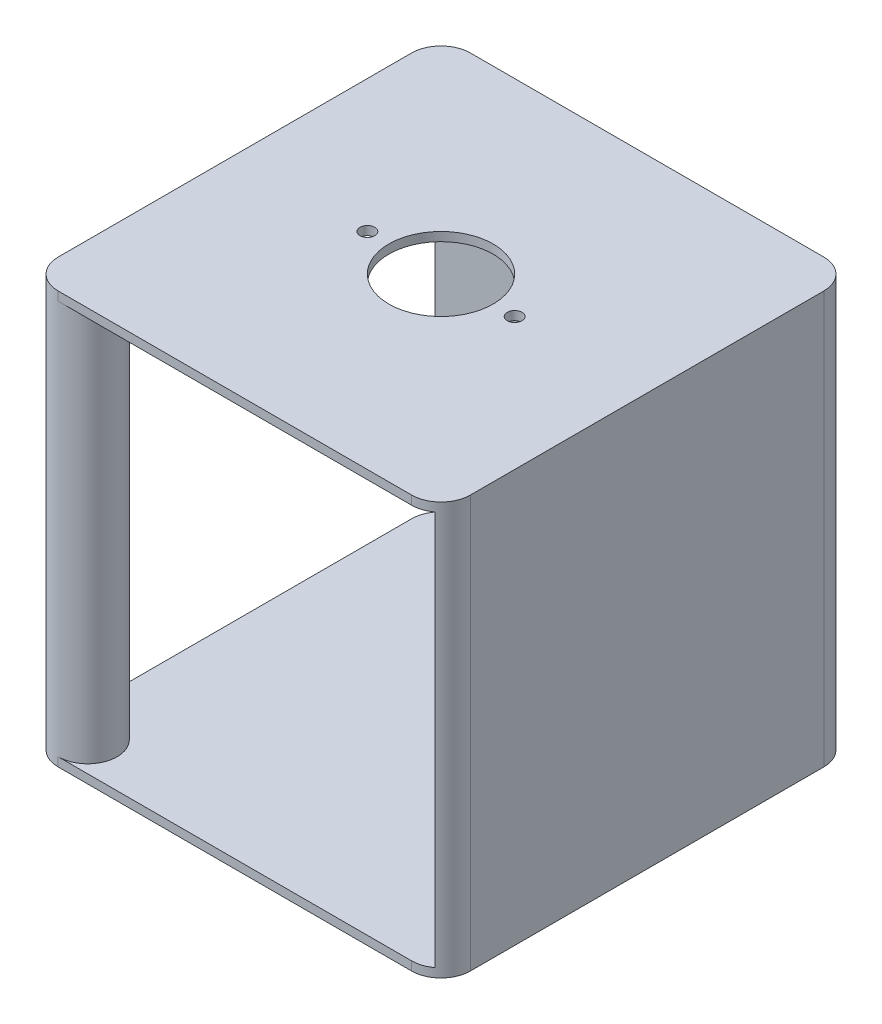
SolidWorks part; units mm, degrees
ref_plane "Front Plane" through (0, 0, 0) normal (0, 0, 1) x (1, 0, 0)
ref_plane "Top Plane" through (0, 0, 0) normal (0, 1, 0) x (1, 0, 0)
ref_plane "Right Plane" through (0, 0, 0) normal (1, 0, 0) x (0, 0, -1)
sketch "Sketch7" plane through (0, 0, 0) normal (0, 1, 0) x (1, 0, 0)
  line L0 (0, 72.4055) -> (0, -69.4849) construction
  line L1 (-87.13, 0) -> (93.2145, 0) construction
  line L2 (-38.1, 44.45) -> (38.1, 44.45)
  line L3 (44.45, 38.1) -> (44.45, -38.1)
  line L4 (-38.1, -44.45) -> (38.1, -44.45)
  line L5 (-44.45, -38.1) -> (-44.45, 38.1)
  arc A0 (-38.1, 44.45) -> (-44.45, 38.1) centre (-38.1, 38.1) ccw
  arc A1 (44.45, 38.1) -> (38.1, 44.45) centre (38.1, 38.1) ccw
  arc A2 (38.1, -44.45) -> (44.45, -38.1) centre (38.1, -38.1) ccw
  arc A3 (-44.45, -38.1) -> (-38.1, -44.45) centre (-38.1, -38.1) ccw
  point P13 (44.45, 0)
  point P14 (0, -44.45)
  point P15 (-44.45, 0)
  point P16 (0, 44.45)
  dimension "D1" = 44.45
  dimension "D2" = 44.45
  dimension "D3" = 44.45
  dimension "D4" = 44.45
  dimension "D5" = 76.2
  dimension "D6" = 76.2
  dimension "D7" = 76.2
  dimension "D8" = 76.2
  dimension "D9" = 6.35
  dimension "D10" = 6.35
  dimension "D11" = 6.35
  dimension "D12" = 6.35
extrude "Boss-Extrude3" add sketch "Sketch7" along normal blind 1.905
extrude "Boss-Extrude4" add sketch "Sketch7<2>" against normal blind 86.995
sketch "Sketch7<2>" plane through (0, 0, 0) normal (0, 1, 0) x (1, 0, 0) same geometry as "Sketch7"
sketch "Sketch15" plane through (0, 0, 0) normal (0, 1, 0) x (1, 0, 0)
  line L1 (-35.56, 41.91) -> (35.56, 41.91)
  line L2 (-41.91, 35.56) -> (-41.91, -35.56)
  line L3 (-35.56, -41.91) -> (35.56, -41.91)
  line L4 (41.91, 35.56) -> (41.91, -35.56)
  line L5 (-41.91, 41.91) -> (41.91, -41.91) construction
  line L6 (-41.91, -41.91) -> (41.91, 41.91) construction
  arc A0 (-41.91, -35.56) -> (-35.56, -41.91) centre (-35.56, -35.56) ccw
  arc A1 (35.56, -41.91) -> (41.91, -35.56) centre (35.56, -35.56) ccw
  arc A2 (35.56, 41.91) -> (41.91, 35.56) centre (35.56, 35.56) cw
  arc A3 (-35.56, 41.91) -> (-41.91, 35.56) centre (-35.56, 35.56) ccw
  point P0 (0, 0)
  dimension "D3" = 6.35
  dimension "D1" = 83.82
  dimension "D2" = 83.82
extrude "Cut-Extrude2" cut sketch "Sketch15" against normal blind 85.09
sketch "Sketch16" plane through (0, 0, 44.45) normal (0, 0, 1) x (1, 0, 0)
  line L0 (48.895, 0) -> (-48.895, 0) construction
  line L1 (38.1, 0) -> (-44.45, 0)
  line L2 (38.1, 0) -> (38.1, -85.09)
  line L3 (38.1, -85.09) -> (-44.45, -85.09)
  line L4 (-44.45, 0) -> (-44.45, -85.09)
  line L5 (38.1, 1.905) -> (38.1, -86.995) construction
  line L6 (-44.45, 1.905) -> (-44.45, -86.995) construction
  dimension "D1" = 85.09
extrude "Cut-Extrude3" cut sketch "Sketch16" against normal blind 86.36
sketch "Sketch18" plane through (41.91, 0, 0) normal (-1, 0, 0) x (0, 0, 1)
  line L0 (48.895, 0) -> (-48.895, 0) construction
  line L1 (44.45, -85.09) -> (-35.56, -85.09)
  line L2 (44.45, -85.09) -> (44.45, 0)
  line L3 (44.45, 0) -> (-35.56, 0)
  line L4 (-35.56, -85.09) -> (-35.56, 0)
  line L5 (-35.56, -85.09) -> (-35.56, 0) construction
extrude "Cut-Extrude4" cut sketch "Sketch18" along normal blind 86.36
sketch "Sketch19" plane through (0, -85.09, 0) normal (0, 1, 0) x (1, 0, 0)
  circle A0 centre (-38.1, -38.1) radius 6.35
  dimension "D1" = 12.7
extrude "Boss-Extrude5" add sketch "Sketch19" along normal blind 86.36
sketch "Sketch20" plane through (0, 1.905, 0) normal (0, 1, 0) x (1, 0, 0)
  line L0 (-54.8357, 0) -> (54.322, 0) construction
  line L1 (0, -50.4052) -> (0, 51.0473) construction
  circle A0 centre (0, 0) radius 11.2395
  circle A1 centre (-15.875, 0) radius 1.5875
  circle A2 centre (15.875, 0) radius 1.5875
  dimension "D1" = 22.479
  dimension "D4" = 3.175
  dimension "D5" = 3.175
  dimension "D2" = 15.875
  dimension "D3" = 15.875
extrude "Cut-Extrude5" cut sketch "Sketch20" against normal up to next
